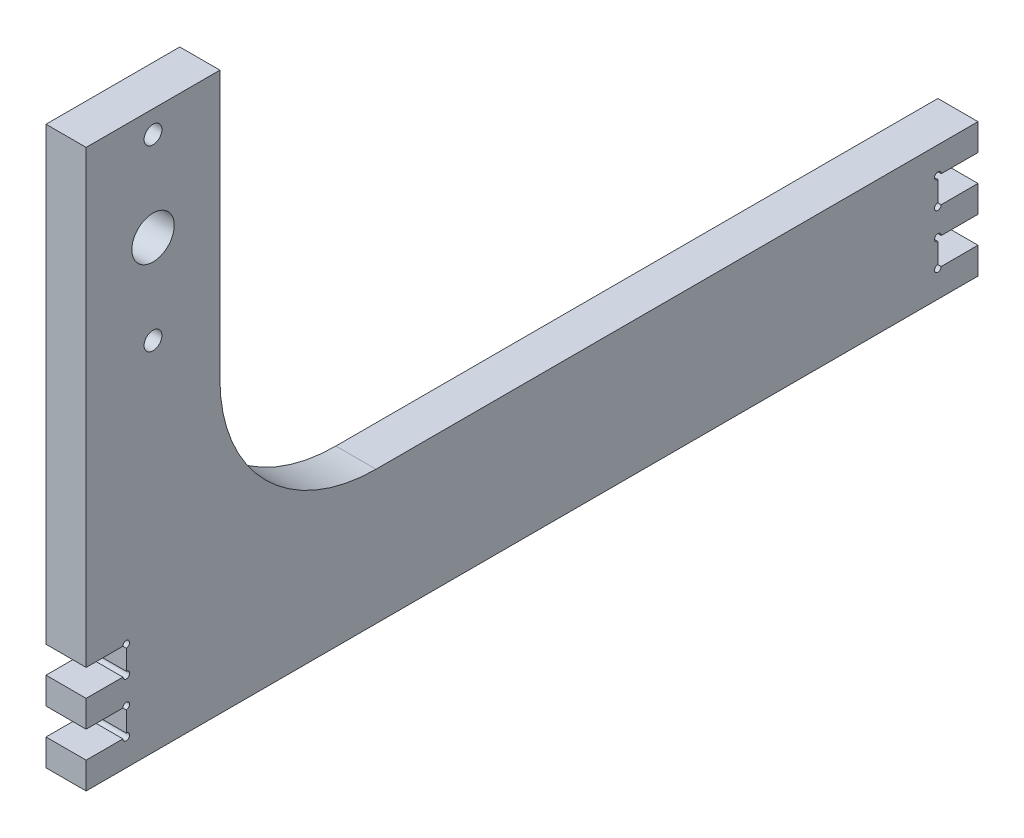
SolidWorks part; units mm, degrees
ref_plane "Front Plane" through (0, 0, 0) normal (0, 0, 1) x (1, 0, 0)
ref_plane "Top Plane" through (0, 0, 0) normal (0, 1, 0) x (1, 0, 0)
ref_plane "Right Plane" through (0, 0, 0) normal (1, 0, 0) x (0, 0, -1)
sketch "Sketch1" plane through (0, 0, 0) normal (1, 0, 0) x (0, 0, -1)
  line L0 (-1000, 0) -> (49000, 0) construction
  line L1 (-30, -250) -> (370, -250)
  line L4 (370, -250) -> (370, -238)
  line L6 (-30, -202) -> (-13.5, -202) construction
  line L7 (0, -1000) -> (0, 49000) construction
  line L9 (-30, 0) -> (-30, -202)
  line L10 (-30, -214) -> (-13.5, -214) construction
  line L11 (-30, -226) -> (-13.5, -226) construction
  line L12 (-30, -238) -> (-13.5, -238) construction
  line L13 (-12, -203.5) -> (-12, -212.5)
  line L14 (-30, -202) -> (-13.5, -202)
  line L15 (-30, -214) -> (-13.5, -214)
  line L16 (-30, -226) -> (-13.5, -226)
  line L17 (-13.5, -238) -> (-30, -238)
  line L20 (0, -750) -> (0, 49250) construction
  line L21 (-12, -227.5) -> (-12, -236.5)
  line L22 (353.5, -238) -> (370, -238)
  line L23 (352, -227.5) -> (352, -236.5)
  line L24 (370, -226) -> (353.5, -226)
  line L25 (370, -214) -> (353.5, -214)
  line L26 (352, -203.5) -> (352, -212.5)
  line L27 (370, -202) -> (353.5, -202)
  line L29 (370, -226) -> (370, -214)
  line L30 (370, -190) -> (370, -202)
  line L31 (30, 0) -> (30, -120)
  line L32 (-30, 0) -> (30, 0)
  line L33 (100, -190) -> (370, -190)
  line L34 (-27.1942, -50) -> (27.1942, -50) construction
  line L35 (-30, -214) -> (-30, -226)
  line L37 (-30, -238) -> (-30, -250)
  line L38 (170, -1250) -> (170, 48750) construction
  circle A1 centre (0, -50) radius 4
  circle A2 centre (0, -90) radius 4
  circle A3 centre (0, -10) radius 4
  arc A5 (100, -190) -> (30, -120) centre (100, -120) cw
  arc A6 (-12, -203.5) -> (-13.5, -202) centre (-12, -202) ccw
  arc A7 (-13.5, -214) -> (-12, -212.5) centre (-12, -214) ccw
  arc A8 (-12, -227.5) -> (-13.5, -226) centre (-12, -226) ccw
  arc A9 (-13.5, -238) -> (-12, -236.5) centre (-12, -238) ccw
  arc A10 (353.5, -202) -> (352, -203.5) centre (352, -202) ccw
  arc A11 (352, -212.5) -> (353.5, -214) centre (352, -214) ccw
  arc A12 (353.5, -226) -> (352, -227.5) centre (352, -226) ccw
  arc A13 (352, -236.5) -> (353.5, -238) centre (352, -238) ccw
  point P0 (0, 0)
  point P51 (0, -50)
  point P52 (170, -250)
  dimension "D7" = 48
  dimension "D14" = 8
  dimension "D16" = 40
  dimension "D18" = 120
  dimension "D12" = 70
  dimension "D13" = 100
  dimension "D20" = 3
  dimension "D25" = 3
  dimension "D2" = 12
  dimension "D3" = 18
  dimension "D4" = 60
  dimension "D5" = 250
  dimension "D6" = 400
  dimension "D8" = 250
  dimension "D9" = 12
  dimension "D11" = 60
  dimension "D10" = 9
  dimension "D15" = 50
  dimension "D17" = 40
  dimension "D19" = 30
  dimension "D21" = 4
  dimension "D22" = 9
  dimension "D23" = 12
  dimension "D24" = 18
  dimension "D27" = 16.5
  dimension "D28" = 200
  dimension "D29" = 18
  dimension "D26" = 4
extrude "Boss-Extrude1" add sketch "Sketch1" along normal blind 18 contours L33 A5 L31 L32 L9 L14 L13 L15 L35 L16 L21 L17 L1 L4 L22 L23 L24 L29 L25 L26 L27 L30 A1 A2 A3 region at (0, -244, 25.283)
sketch "Sketch3" plane through (18, 0, 0) normal (1, 0, 0) x (0, 0, -1)
  circle A0 centre (0, -50) radius 9.5
  dimension "D1" = 19
extrude "Cut-Extrude1" cut sketch "Sketch3" against normal up to next
